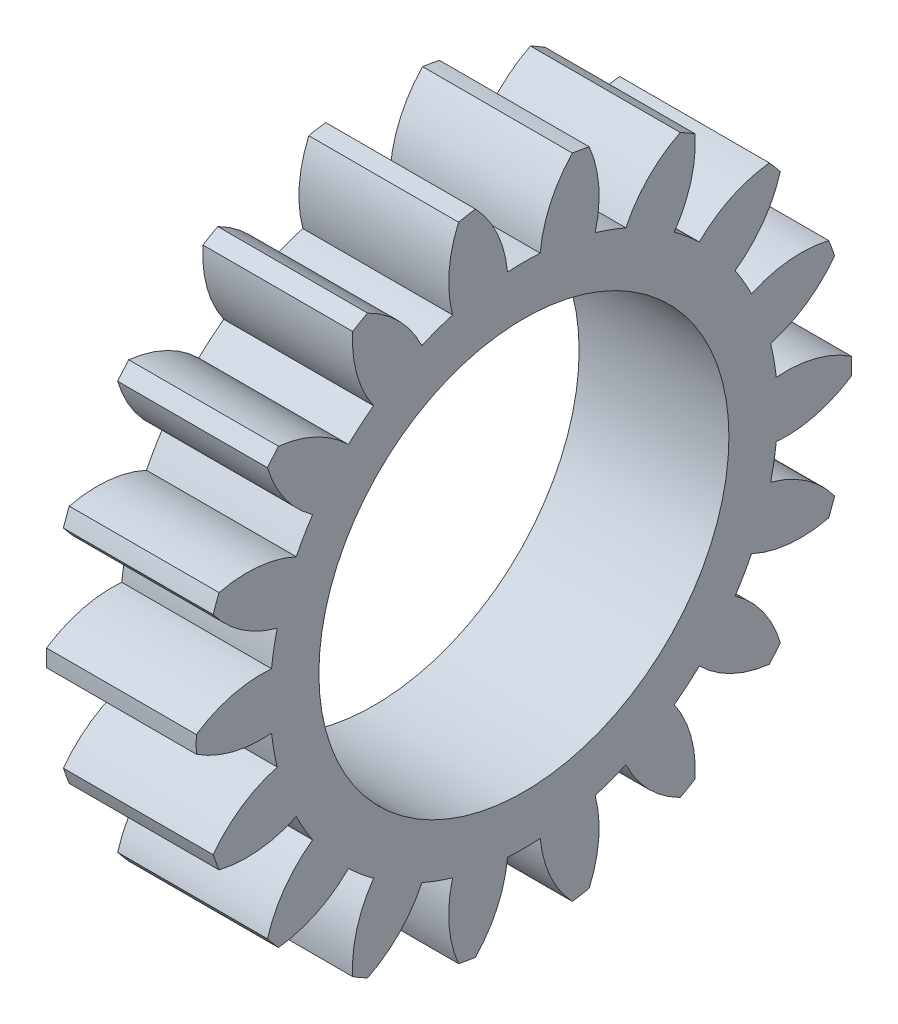
SolidWorks part; units mm, degrees
material "PLA personnalisé"
ref_plane "Plane1" through (0, 0, 0) normal (0, 0, 1) x (1, 0, 0)
ref_plane "Plane2" through (0, 0, 0) normal (0, 1, 0) x (1, 0, 0)
ref_plane "Plane3" through (0, 0, 0) normal (1, 0, 0) x (0, 0, -1)
other "Configuration Table"
sketch "HoldingSke" plane through (0, 0, 0) normal (0, 1, 0) x (1, 0, 0)
  line L0 (0, 0) -> (0.5435, -0.1766)
  line L1 (-15, 0) -> (100, 0) construction
  line L2 (0, 0) -> (-2.1039, 2.3779)
  line L3 (0, 0) -> (-11.863, 4.5341)
  line L4 (0, 0) -> (8.2133, 2.6687)
  line L5 (0, 0) -> (-46.8476, -17.4728)
  line L6 (0, 0) -> (-6.6317, -4.4744)
  line L7 (-2.1039, 2.3779) -> (8.6586, 51.2059)
  line L8 (-76.2, 54.61) -> (-74.8, 54.61)
  line L9 (-71.009, 38.7566) -> (-53.1078, 45.2721)
  line L10 (-76.2, 71.12) -> (104.1128, 71.12)
  line L11 (0, 0) -> (-8, 0)
  line L12 (-76.2, 101.6) -> (-76.147, 101.6)
  line L13 (24.9733, 27.94) -> (52.9518, 28.4284)
  line L14 (24.9733, 27.94) -> (24.9743, 27.94)
  line L15 (24.9733, 27.94) -> (100.4006, 29.5858)
  line L16 (-63.627, -1.75) -> (-12.827, -1.75)
  circle A0 centre (0, 0) radius 4
  circle A1 centre (0, 0) radius 13.5615
  circle A2 centre (0, 0) radius 37.5
  circle A3 centre (0, 0) radius 4
  dimension "MHD" = 27.123
  dimension "Hub_dia" = 75
  dimension "Bore" = 8
  dimension "MBD" = 8
  dimension "Num_teeth" = 18
  dimension "Pitch" = 0.5714
  dimension "Overall_len" = 50
  dimension "Show_teeth" = 18
  dimension "Thickness" = 8
  dimension "OAL" = 50.0001
  dimension "T_dim" = 1.4
  dimension "Ap" = 20
  dimension "H" = 19.05
  dimension "Pitch_radius" = 180.3128
  dimension "Width" = 8
  dimension "Backlash" = 0.053
  dimension "Addendum_fac" = 1
  dimension "Dedendum_fac" = 1.25
  dimension "Clearance_fac" = 0.25
  dimension "Dedendum_add" = 0.001
  dimension "Module" = 1.75
sketch "BasProSke" plane through (0, 0, 0) normal (0, 1, 0) x (1, 0, 0)
  line L0 (-10, 0) -> (60, 0) construction
  line L1 (0, 0) -> (0, 17.5)
  line L2 (0, 0) -> (8, 0)
  line L3 (8, 0) -> (8, 17.5)
  line L4 (8, 17.5) -> (0, 17.5)
  dimension "Thickness" = 8
  dimension "Diameter" = 35
revolve "Base-Revolve" add sketch "BasProSke" angle 360 about L0
sketch "TooCutSke" plane through (0, 0, 0) normal (1, 0, 0) x (0, 0, -1)
  line L1 (0, 0) -> (0, 107) construction
  line L2 (0, 0) -> (-1.4654, 15.6817) construction
  line L3 (0, 0) -> (-5.4518, 30.9188) construction
  line L4 (-1.4654, 15.6817) -> (-2.7259, 15.4594) construction
  arc A0 (0.8733, 13.5334) -> (-0.8733, 13.5334) centre (0, 0) ccw
  arc A1 (2.6093, 17.3301) -> (-2.6093, 17.3301) centre (0, 0) ccw
  circle A2 centre (0, 0) radius 15.75 construction
  circle A3 centre (0, 0) radius 14.8002 construction
  arc A4 (-0.8733, 13.5334) -> (-2.6093, 17.3301) centre (-7.1472, 12.96) ccw
  arc A5 (2.6093, 17.3301) -> (0.8733, 13.5334) centre (7.1472, 12.96) ccw
  dimension "Root_dia" = 27.123
  dimension "Overcut_dia" = 35.0508
  dimension "Pitch_dia" = 31.5
  dimension "Base_dia" = 29.6003
  dimension "Flank_rad" = 6.3
  dimension "Half_ang" = 10
  dimension "Half_CT" = 1.28
extrude "ToothCut" cut sketch "TooCutSke" along normal through all
fillet "Breaks" [suppressed] radius 0.035 tangent propagation no
fillet "RootFillets" [suppressed] radius 0.4385
pattern_circular "TeethCuts" count 18 every 20 about axis through (-10, 0, 0) along (1, 0, 0) of "ToothCut", "RootFillets", "Breaks"
sketch "HubNeaOneSke" plane through (0, 0, 0) normal (-1, 0, 0) x (0, 0, 1)
  circle A0 centre (0, 0) radius 13.5615
  dimension "Diameter" = 27.123
extrude "HubNearOne" [suppressed] add sketch "HubNeaOneSke" along normal blind 42.0001
sketch "HubNeaBotSke" plane through (0, 0, 0) normal (-1, 0, 0) x (0, 0, 1)
  circle A0 centre (0, 0) radius 13.5615
  dimension "Diameter" = 27.123
extrude "HubNearBoth" [suppressed] add sketch "HubNeaBotSke" along normal blind 21
ref_plane "FarPln" through (8, 0, 0) normal (1, 0, 0) x (0, 0, -1)
sketch "HubFarSke" plane through (8, 0, 0) normal (1, 0, 0) x (0, 0, -1)
  circle A0 centre (0, 0) radius 13.5615
  dimension "Diameter" = 27.123
extrude "HubFar" [suppressed] add sketch "HubFarSke" along normal blind 21
sketch "BorSke" plane through (0, 0, 0) normal (1, 0, 0) x (0, 0, -1)
  circle A0 centre (0, 0) radius 4
  dimension "Diameter" = 8
extrude "Bore" cut sketch "BorSke" along normal mid plane 100.0001
sketch "KeySke" plane through (0, 0, 0) normal (1, 0, 0) x (0, 0, -1)
  line L0 (-1.5, 0) -> (-1.5, 5.4)
  line L1 (-1.5, 5.4) -> (1.5, 5.4)
  line L2 (1.5, 5.4) -> (1.5, 0)
  line L3 (0, 0) -> (0, 34) construction
  line L4 (-1.5, 0) -> (1.5, 0)
  dimension "Offset" = 5.4
  dimension "Width" = 3
extrude "Keyway" [suppressed] cut sketch "KeySke" along normal mid plane 100.0001
pattern_circular "Keyway2" [suppressed] count 2 every 90 about axis through (-10, 0, 0) along (1, 0, 0) reverse direction yes
sketch "Esquisse1" plane through (8, 0, 0) normal (1, 0, 0) x (0, 0, -1)
  circle A0 centre (0, 0) radius 10.95
  dimension "D1" = 21.9
extrude "Enlèv. mat.-Extru.1" cut sketch "Esquisse1" against normal blind 10
equation "' \"Module@HoldingSke\" = 6.35"
equation "' \"Num_teeth@HoldingSke\" = 12"
equation "' \"Ap@HoldingSke\" =  20"
equation "' \"Ap@HoldingSke\" = 20"
equation "' \"Width@HoldingSke\" = 0.5 * 25.4"
equation "' \"Hub_dia@HoldingSke\"= 1 * 25.4"
equation "' \"Hub_dia@HoldingSke\" = 1 * 25.4"
equation "' \"Overall_len@HoldingSke\" = 1.0 * 25.4"
equation "' \"Bore@HoldingSke\" = 0.75 * 25.4"
equation "' \"T_dim@HoldingSke\" = 0.1 * 25.4"
equation "' \"Width@KeySke\" = 0.25 * 25.4"
equation "' \"Show_teeth@HoldingSke\" = 13"
equation "' \"Backlash@HoldingSke\" = 0.009 * 25.4"
equation "' \"Addendum_fac@HoldingSke\" = 1.0"
equation "' \"Dedendum_fac@HoldingSke\" = 1.25"
equation "' \"Dedendum_add@HoldingSke\" = 0.00005 * 25.4"
equation "' \"Clearance_fac@HoldingSke\" = 0.25"
equation "\"Pitch@HoldingSke\" = 1 / \"Module@HoldingSke\""
equation "\"Overcut_dia@TooCutSke\" = (\"Num_teeth@HoldingSke\" + 2 * \"Addendum_fac@HoldingSke\") / \"Pitch@HoldingSke\" + 0.002 * 25.4"
equation "\"Pitch_dia@TooCutSke\" = \"Num_teeth@HoldingSke\" / \"Pitch@HoldingSke\""
equation "\"Base_dia@TooCutSke\" = \"Num_teeth@HoldingSke\" / \"Pitch@HoldingSke\" * cos((\"Ap@HoldingSke\"  * 3.14159265 / 180))"
equation "\"Root_dia@TooCutSke\" = (\"Num_teeth@HoldingSke\" + 2) / \"Pitch@HoldingSke\" - 2 * (\"Addendum_fac@HoldingSke\" + \"Dedendum_fac@HoldingSke\") / \"Pitch@HoldingSke\" - \"Dedendum_add@HoldingSke\" * 2"
equation "\"Half_ang@TooCutSke\" = 180 / \"Num_teeth@HoldingSke\""
equation "\"Half_CT@TooCutSke\" = \"Num_teeth@HoldingSke\" / \"Pitch@HoldingSke\" * sin((3.14159265 / 2 / \"Num_teeth@HoldingSke\")) / 2 - 7 * \"Backlash@HoldingSke\" / 4"
equation "\"Flank_rad@TooCutSke\" = \"Num_teeth@HoldingSke\" / \"Pitch@HoldingSke\" / 5"
equation "\"Radius@RootFillets\" = \"Clearance_fac@HoldingSke\" / \"Pitch@HoldingSke\" + \"Dedendum_add@HoldingSke\""
equation "\"Break_rad@Breaks\" = 0.02 / \"Pitch@HoldingSke\""
equation "\"Thickness@HoldingSke\" = \"Width@HoldingSke\""
equation "\"OAL@HoldingSke\" = \"Thickness@HoldingSke\""
equation "\"MHD@HoldingSke\" = (\"Num_teeth@HoldingSke\" + 2) / \"Pitch@HoldingSke\" - 2 * (\"Addendum_fac@HoldingSke\" + \"Dedendum_fac@HoldingSke\")  / \"Pitch@HoldingSke\" - \"Dedendum_add@HoldingSke\" * 2"
equation "\"MBD@HoldingSke\" = (\"Num_teeth@HoldingSke\" + 2) / \"Pitch@HoldingSke\" - 2 * (\"Addendum_fac@HoldingSke\" + \"Dedendum_fac@HoldingSke\")  / \"Pitch@HoldingSke\" - \"Dedendum_add@HoldingSke\" * 2 - 0.002 * 25.4"
equation "\"MHD@HoldingSke\" = ((sgn( \"MHD@HoldingSke\" - \"Hub_dia@HoldingSke\" )-1)*( \"MHD@HoldingSke\" - \"Hub_dia@HoldingSke\" ))/-2+ \"Hub_dia@HoldingSke\""
equation "\"MBD@HoldingSke\" = ((sgn( \"MBD@HoldingSke\" - \"Bore@HoldingSke\" )-1)*( \"MBD@HoldingSke\" - \"Bore@HoldingSke\" ))/-2+ \"Bore@HoldingSke\""
equation "\"OAL@HoldingSke\" = ((sgn( \"OAL@HoldingSke\" - \"Overall_len@HoldingSke\" )+1)*( \"OAL@HoldingSke\" - \"Overall_len@HoldingSke\" ))/2 + \"Overall_len@HoldingSke\" + 0.000002 * 25.4"
equation "\"Num_teeth@TeethCuts\" = int( \"Show_teeth@HoldingSke\" ) + 1"
equation "\"Num_teeth@TeethCuts\" = ((sgn( \"Num_teeth@TeethCuts\" - \"Num_teeth@HoldingSke\" )-1)*( \"Num_teeth@TeethCuts\" - \"Num_teeth@HoldingSke\" ))/-2+ \"Num_teeth@HoldingSke\""
equation "\"Num_teeth@TeethCuts\" = ((sgn( \"Num_teeth@TeethCuts\" - 2.0)+1)*( \"Num_teeth@TeethCuts\" - 2.0))/2 +2.0"
equation "\"Angle@TeethCuts\" = 360.0 / \"Num_teeth@HoldingSke\""
equation "\"Diameter@BasProSke\" = (\"Num_teeth@HoldingSke\" + 2 * \"Addendum_fac@HoldingSke\") / \"Pitch@HoldingSke\""
equation "\"Thickness@BasProSke\"  = \"Thickness@HoldingSke\""
equation "' \"Fillet_rad@BasProSke\" =  \"Thickness@HoldingSke\" * 0.05"
equation "' \"Fillet_rad@BasProSke\" = \"Thickness@HoldingSke\" * 0.05"
equation "\"MHD@HoldingSke\" = ((sgn( \"MHD@HoldingSke\" - \"Root_dia@TooCutSke\" )-1)*( \"MHD@HoldingSke\" - \"Root_dia@TooCutSke\" ))/-2+ \"Root_dia@TooCutSke\""
equation "\"Diameter@HubNeaOneSke\" = \"MHD@HoldingSke\""
equation "\"Length@HubNearOne\" = \"OAL@HoldingSke\" - \"Thickness@BasProSke\""
equation "\"Diameter@HubNeaBotSke\" = \"MHD@HoldingSke\""
equation "\"Length@HubNearBoth\" = ( \"OAL@HoldingSke\" - \"Thickness@BasProSke\" ) / 2.0"
equation "\"Thickness@FarPln\" = \"Thickness@BasProSke\""
equation "\"Diameter@HubFarSke\" = \"MHD@HoldingSke\""
equation "\"Length@HubFar\" = ( \"OAL@HoldingSke\" - \"Thickness@BasProSke\" ) / 2.0"
equation "\"Diameter@BorSke\" = \"MBD@HoldingSke\""
equation "\"D1@Bore\" = \"OAL@HoldingSke\" * 2.0"
equation "\"D1@Keyway\" = \"OAL@HoldingSke\" * 2.0"
equation "\"Offset@KeySke\" = \"T_dim@HoldingSke\" + \"MBD@HoldingSke\" / 2.0"
